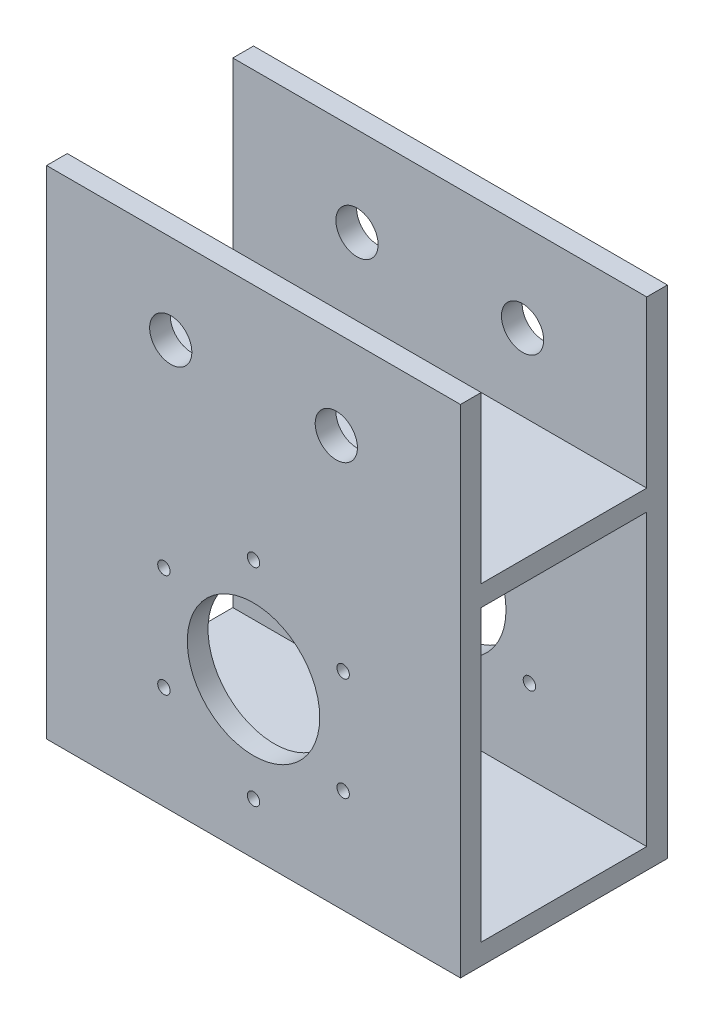
SolidWorks part; units mm, degrees
ref_plane "Front Plane" through (0, 0, 0) normal (0, 0, 1) x (1, 0, 0)
ref_plane "Top Plane" through (0, 0, 0) normal (0, 1, 0) x (1, 0, 0)
ref_plane "Right Plane" through (0, 0, 0) normal (1, 0, 0) x (0, 0, -1)
sketch "Sketch1" plane through (0, 0, 0) normal (0, 0, 1) x (1, 0, 0)
  line L1 (-50, 60) -> (50, 60)
  line L2 (-50, 60) -> (-50, -60)
  line L3 (-50, -60) -> (50, -60)
  line L4 (50, 60) -> (50, -60)
  line L5 (-50, 60) -> (50, -60) construction
  line L6 (-50, -60) -> (50, 60) construction
  point P0 (0, 0)
  dimension "D1" = 100
  dimension "D2" = 120
extrude "Boss-Extrude1" add sketch "Sketch1" along normal blind 5
sketch "Sketch2" plane through (0, 0, 5) normal (0, 0, 1) x (1, 0, 0)
  line L0 (-50, 60) -> (-50, -60) construction
  line L1 (-50, 20) -> (50, 20)
  line L2 (-50, 20) -> (-50, 15)
  line L3 (-50, 15) -> (50, 15)
  line L4 (50, 20) -> (50, 15)
  line L5 (50, -60) -> (50, 60) construction
  line L6 (50, 60) -> (-50, 60) construction
  dimension "D1" = 5
  dimension "D2" = 40
extrude "Boss-Extrude2" add sketch "Sketch2" along normal blind 45
sketch "Sketch3" plane through (0, 20, 0) normal (0, 1, 0) x (1, 0, 0)
  line L0 (50, -50) -> (50, -5) construction
  line L1 (-50, -50) -> (50, -50)
  line L2 (-50, -50) -> (-50, -45)
  line L3 (-50, -45) -> (50, -45)
  line L4 (50, -50) -> (50, -45)
  dimension "D1" = 5
extrude "Boss-Extrude3" add sketch "Sketch3" along normal blind 40 and the other way blind 60
sketch "Sketch6" plane through (0, -40, 0) normal (0, -1, 0) x (1, 0, 0)
  line L1 (-50, 45) -> (50, 45)
  line L2 (-50, 45) -> (-50, 50)
  line L3 (-50, 50) -> (50, 50)
  line L4 (50, 45) -> (50, 50)
  line L5 (-50, 0) -> (50, 0)
  line L6 (-50, 0) -> (-50, 5)
  line L7 (-50, 5) -> (50, 5)
  line L8 (50, 0) -> (50, 5)
extrude "Boss-Extrude4" add sketch "Sketch6" along normal blind 15
sketch "Sketch7" plane through (0, 0, 5) normal (0, 0, 1) x (1, 0, 0)
  line L6 (50, -60) -> (50, 15) construction
  line L7 (-50, -60) -> (50, -60)
  line L8 (-50, -60) -> (-50, -55)
  line L9 (-50, -55) -> (50, -55)
  line L10 (50, -60) -> (50, -55)
  dimension "D1" = 5
extrude "Boss-Extrude5" add sketch "Sketch7" along normal blind 45
sketch "Sketch8" plane through (0, 0, 50) normal (0, 0, 1) x (1, 0, 0)
  line L0 (-50, 15) -> (50, 15) construction
  line L1 (-50, 60) -> (-50, -60) construction
  line L2 (50, -60) -> (50, 60) construction
  line L3 (-50, -60) -> (50, -60) construction
  circle A1 centre (0, -22.5) radius 16
  circle A2 centre (0, -22.5) radius 25 construction
  circle A3 centre (0, 2.5) radius 1.5
  circle A4 centre (21.6506, -10) radius 1.5
  circle A5 centre (21.6506, -35) radius 1.5
  circle A6 centre (0, -47.5) radius 1.5
  circle A7 centre (-21.6506, -35) radius 1.5
  circle A8 centre (-21.6506, -10) radius 1.5
  point P26 (0, -22.5)
  dimension "D1" = 32
  dimension "D4" = 50
  dimension "D2" = 37.5
  dimension "D3" = 75
extrude "Cut-Extrude1" cut sketch "Sketch8" against normal through all
sketch "Sketch9" plane through (0, 0, 50) normal (0, 0, 1) x (1, 0, 0)
  line L0 (0, 60) -> (0, -60) construction
  line L1 (-50, 60) -> (50, 60) construction
  line L2 (-50, -60) -> (50, -60) construction
sketch "Sketch10" plane through (0, 0, 50) normal (0, 0, 1) x (1, 0, 0)
  line L0 (0, 60) -> (0, -60) construction
  circle A0 centre (-20, 38.4946) radius 5.1
  circle A1 centre (20, 38.4946) radius 5.1
  dimension "D1" = 10.2
  dimension "D2" = 10.2
  dimension "D3" = 40
  dimension "D4" = 20
extrude "Cut-Extrude2" cut sketch "Sketch10" against normal through all
